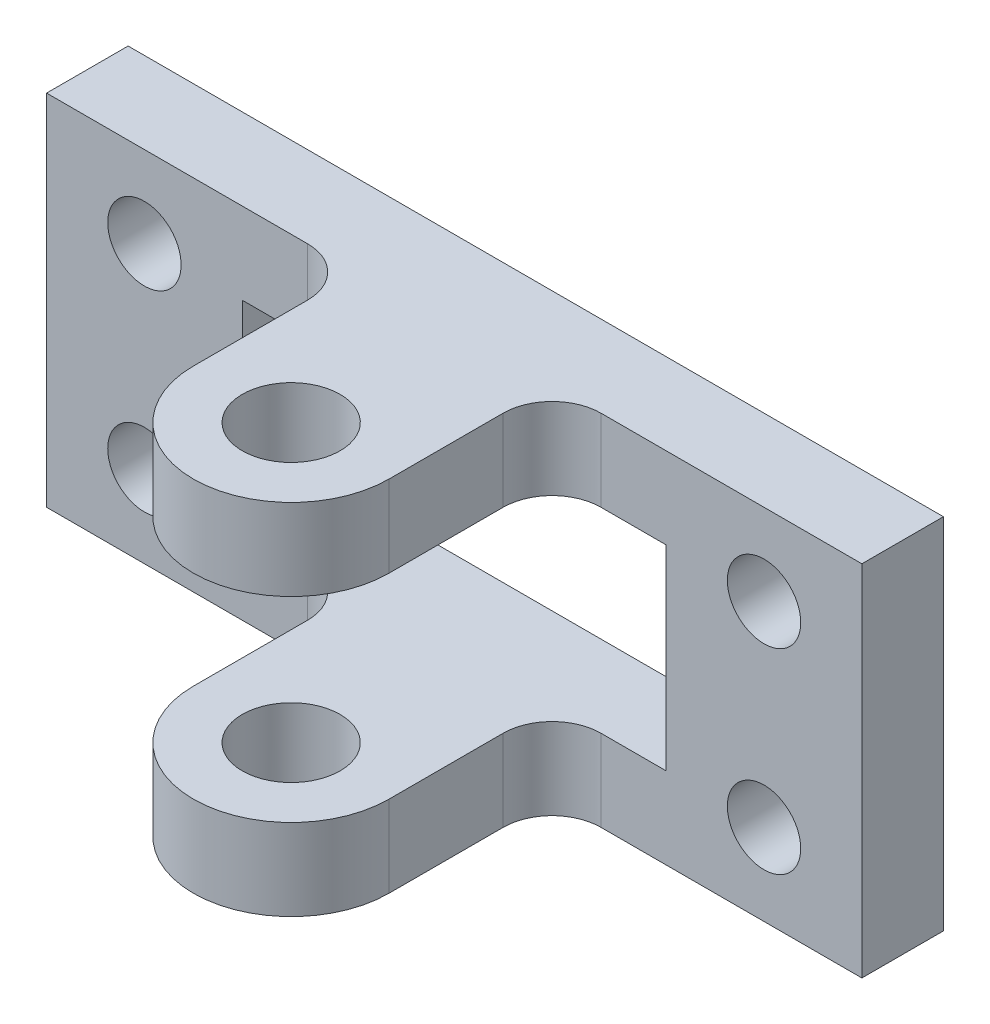
SolidWorks part; units mm, degrees
ref_plane "前视基准面" through (0, 0, 0) normal (0, 0, 1) x (1, 0, 0)
ref_plane "上视基准面" through (0, 0, 0) normal (0, 1, 0) x (1, 0, 0)
ref_plane "右视基准面" through (0, 0, 0) normal (1, 0, 0) x (0, 0, -1)
ref_plane "基准面1" through (0, 0, 15) normal (0, 0, -1) x (-1, 0, 0)
sketch "草图1" plane through (0, 0, 15) normal (0, 0, -1) x (-1, 0, 0)
  line L0 (6, -6) -> (0, -6)
  line L1 (0, -6) -> (0, -11)
  line L2 (0, -11) -> (6, -11)
  line L3 (6, -11) -> (6, -6)
  line L4 (0, -6) -> (0, -11) construction
revolve "旋转1" add sketch "草图1" angle 180 about L4 reverse direction yes
sketch "草图2" plane through (0, 0, 15) normal (0, 0, -1) x (-1, 0, 0)
  line L0 (6, -6) -> (6, -11)
  line L1 (6, -11) -> (-6, -11)
  line L2 (-6, -11) -> (-6, -6)
  line L3 (-6, -6) -> (6, -6)
extrude "凸台-拉伸1" add sketch "草图2" along normal blind 15
sketch "草图3" plane through (-6, 0, 0) normal (-1, 0, 0) x (0, 0, 1)
  line L0 (5, -6) -> (5, -11)
  line L1 (5, -11) -> (0, -11)
  line L2 (0, -11) -> (0, -6)
  line L3 (0, -6) -> (5, -6)
extrude "凸台-拉伸2" add sketch "草图3" along normal blind 19
sketch "草图4" plane through (6, 0, 0) normal (1, 0, 0) x (0, 0, -1)
  line L0 (0, -6) -> (0, -11)
  line L1 (0, -11) -> (-5, -11)
  line L2 (-5, -11) -> (-5, -6)
  line L3 (-5, -6) -> (0, -6)
extrude "凸台-拉伸3" add sketch "草图4" along normal blind 19
sketch "草图5" plane through (0, -6, 0) normal (0, 1, 0) x (-1, 0, 0)
  line L0 (-25, 5) -> (-13, 5)
  line L1 (-13, 5) -> (-13, 0)
  line L2 (-13, 0) -> (-25, 0)
  line L3 (-25, 0) -> (-25, 5)
extrude "凸台-拉伸4" add sketch "草图5" along normal blind 12
sketch "草图6" plane through (0, -6, 0) normal (0, 1, 0) x (-1, 0, 0)
  line L0 (25, 0) -> (13, 0)
  line L1 (13, 0) -> (13, 5)
  line L2 (13, 5) -> (25, 5)
  line L3 (25, 5) -> (25, 0)
extrude "凸台-拉伸5" add sketch "草图6" along normal blind 12
sketch "草图7" plane through (0, 6, 0) normal (0, 1, 0) x (-1, 0, 0)
  line L0 (25, 5) -> (25, 0)
  line L1 (25, 0) -> (-25, 0)
  line L2 (-25, 0) -> (-25, 5)
  line L3 (-25, 5) -> (-6, 5)
  line L4 (-6, 5) -> (-6, 15)
  line L5 (6, 15) -> (6, 5)
  line L6 (6, 5) -> (25, 5)
  arc A0 (-6, 15) -> (6, 15) centre (0, 15) cw
extrude "凸台-拉伸6" add sketch "草图7" along normal blind 5
hole_wizard "Ø6.0 (6) 直径孔1" positions "草图9" profile "草图8" hole size "Ø6.0" standard "ANSI Metric"
sketch "草图9" plane through (0, 6, 0) normal (0, -1, 0) x (-1, 0, 0)
  point P0 (0, -15)
sketch "草图8" plane through (0, 6, 15) normal (1, 0, 0) x (0, 0, -1)
  line L0 (0, 0) -> (0, 5)
  line L1 (0, 5) -> (3, 5)
  line L2 (3, 5) -> (3, 0)
  line L5 (3, 0) -> (0, 0)
  line L11 (0, -6.35) -> (0, 107.95) construction
  dimension "通孔孔直径" = 6
  dimension "通孔孔深度" = 5
hole_wizard "Ø6.0 (6) 直径孔2" positions "草图13" profile "草图12" hole size "Ø6.0" standard "ANSI Metric"
sketch "草图13" plane through (0, -11, 0) normal (0, -1, 0) x (-1, 0, 0)
  point P0 (0, -15)
sketch "草图12" plane through (0, -11, 15) normal (1, 0, 0) x (0, 0, -1)
  line L0 (0, 0) -> (0, 22)
  line L1 (0, 22) -> (3, 22)
  line L2 (3, 22) -> (3, 0)
  line L5 (3, 0) -> (0, 0)
  line L11 (0, -6.35) -> (0, 107.95) construction
  dimension "通孔孔直径" = 6
  dimension "通孔孔深度" = 22
hole_wizard "Ø4.5 (4.5) 直径孔1" positions "草图15" profile "草图14" hole size "Ø4.5" standard "ANSI Metric" end condition through all
sketch "草图15" plane through (0, 0, 0) normal (0, 0, -1) x (-1, 0, 0)
  point P0 (-19, -6)
  point P1 (19, 6)
  point P2 (19, -6)
  point P3 (-19, 6)
sketch "草图14" plane through (19, -6, 0) normal (1, 0, 0) x (0, 1, 0)
  line L0 (0, 0) -> (0, 21)
  line L1 (0, 21) -> (2.25, 21)
  line L2 (2.25, 21) -> (2.25, 0)
  line L5 (2.25, 0) -> (0, 0)
  line L11 (0, -6.35) -> (0, 107.95) construction
  dimension "通孔孔直径" = 4.5
  dimension "通孔孔深度" = 21
fillet "圆角1" radius 3 4 edges at (-6, 8.5, 5) (6, 8.5, 5) (-6, -8.5, 5) (6, -8.5, 5) tangent propagation no
